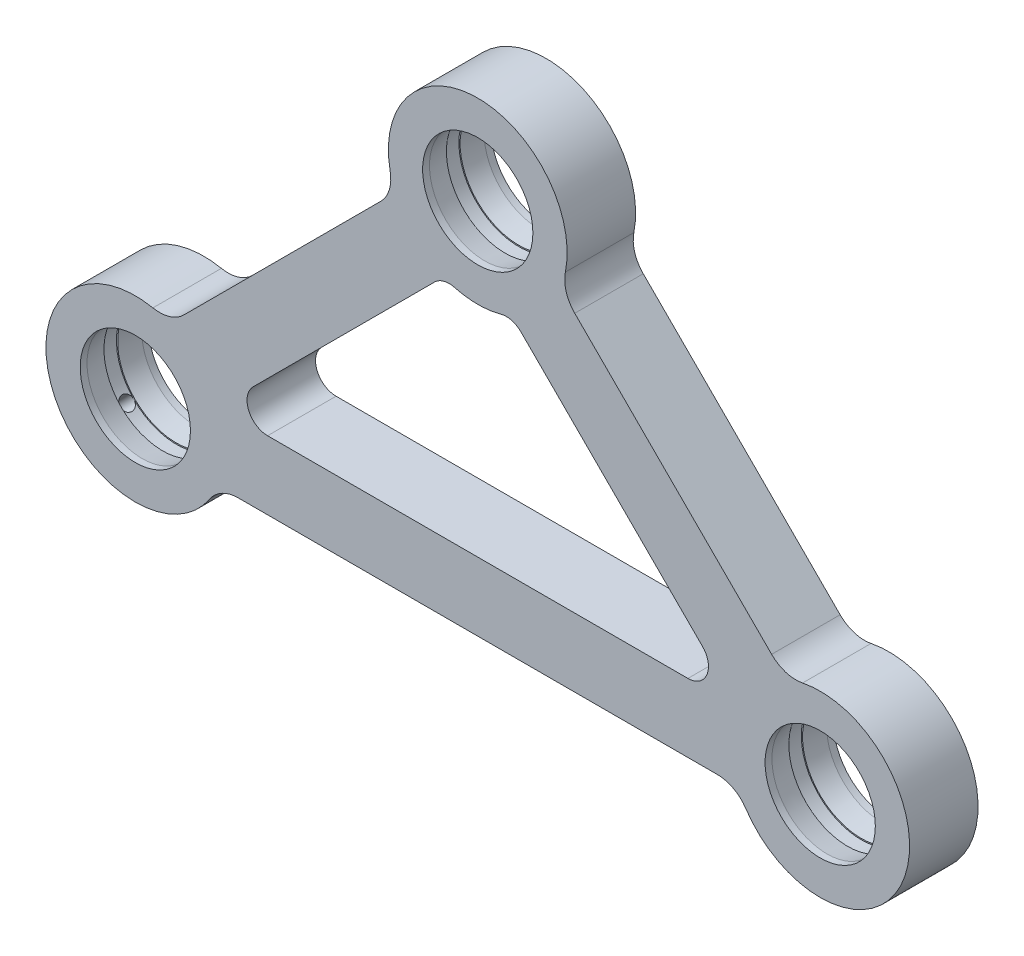
SolidWorks part; units mm, degrees
ref_plane "Front Plane" through (0, 0, 0) normal (0, 0, 1) x (1, 0, 0)
ref_plane "Top Plane" through (0, 0, 0) normal (0, 1, 0) x (1, 0, 0)
ref_plane "Right Plane" through (0, 0, 0) normal (1, 0, 0) x (0, 0, -1)
sketch "Sketch1" plane through (0, 0, 0) normal (0, 0, 1) x (1, 0, 0)
  line L0 (-26.538, 0) -> (73.462, 0) construction
  line L2 (-26.538, 0) -> (23.462, 50) construction
  line L3 (23.462, 50) -> (73.462, 0) construction
  line L4 (-14.4839, 5) -> (61.4078, 5)
  line L5 (-14.4839, -5) -> (61.4078, -5)
  line L6 (-21.55, 12.0591) -> (11.4029, 45.012)
  line L7 (18.474, 37.9409) -> (-14.4789, 4.988)
  line L8 (28.45, 37.9409) -> (61.4029, 4.988)
  line L9 (35.5211, 45.012) -> (68.474, 12.0591)
  circle A0 centre (23.462, 50) radius 8.05
  circle A1 centre (73.462, 0) radius 8.05
  circle A2 centre (-26.538, 0) radius 8.05
  circle A3 centre (-26.538, 0) radius 13.05
  circle A4 centre (23.462, 50) radius 13.05
  circle A5 centre (73.462, 0) radius 13.05
  dimension "D1" = 16.1
  dimension "D2" = 16.1
  dimension "D3" = 16.1
  dimension "D4" = 45
  dimension "D5" = 45
  dimension "D6" = 100
  dimension "D7" = 5
  dimension "D8" = 5
  dimension "D9" = 5
  dimension "D10" = 5
  dimension "D11" = 5
  dimension "D12" = 5
  dimension "D13" = 5
  dimension "D14" = 5
  dimension "D15" = 5
extrude "Boss-Extrude1" add sketch "Sketch1" along normal blind 8 contours A3 A2 | A4 L6 A3 L4 L7 | A4 A0 | A5 L9 A4 L8 L4 | A5 L8 L4 L7 A3 L5 | A5 A1 | A3 L7 L4 | A5 L4 L8 region at (-1.538, 25, 0) region at (-14.4766, 4.996, 0) region at (-14.8224, 4.8528, 0) region at (23.462, 0, 0) region at (48.462, 25, 0) region at (61.4006, 4.996, 0) region at (14.4953, 41.0333, 0) region at (64.4997, 8.9712, 0)
sketch3d "3DSketch1" plane through (0, 0, 0) normal (0, 0, 1) x (1, 0, 0)
  dimension "D1" = 4
sketch "Sketch3" plane through (0, 0, 4) normal (0, 0, 1) x (1, 0, 0)
  circle A0 centre (-26.538, 0) radius 8.7553
  circle A1 centre (23.462, 50) radius 8.7553
  circle A2 centre (73.462, 0) radius 8.7553
  circle A3 centre (-26.538, 0) radius 8.05 construction
  circle A4 centre (23.462, 50) radius 8.05 construction
  circle A5 centre (73.462, 0) radius 8.05 construction
  dimension "D1" = 0.7053
  dimension "D2" = 0.7053
  dimension "D3" = 0.7053
extrude "Cut-Extrude1" cut sketch "Sketch3" against normal blind 1 and the other way blind 1 contours A1 | A0 | A2
sketch3d "3DSketch2" plane through (0, 0, 0) normal (0, 0, 1) x (1, 0, 0)
sketch3d "3DSketch3" plane through (0, 0, 0) normal (0, 0, 1) x (1, 0, 0)
  dimension "D1" = 26
sketch "Sketch4" plane through (0, 62.95, 0) normal (0, -1, 0) x (-1, 0, 0)
  line L0 (-41.8, -4) -> (41.8, -4) construction
  line L1 (-86.512, 0) -> (-86.512, -8) construction
  line L4 (-36.5118, -8) -> (-68.474, -8)
  line L5 (-36.5118, -8) -> (-68.474, -8)
  line L6 (-68.474, -8) -> (-86.512, -8)
  line L7 (-68.474, -8) -> (-86.512, -8)
  line L8 (-86.512, -8) -> (-86.512, 0)
  line L9 (-86.512, -8) -> (-86.512, 0)
  line L10 (-86.512, 0) -> (-68.474, 0)
  line L11 (-86.512, 0) -> (-68.474, 0)
  line L12 (-68.474, 0) -> (-36.5118, 0)
  line L13 (-68.474, 0) -> (-36.5118, 0)
  line L14 (-36.5118, 0) -> (-10.4122, 0)
  line L15 (-36.5118, 0) -> (-10.4122, 0)
  line L16 (-10.4122, 0) -> (21.55, 0)
  line L17 (-10.4122, 0) -> (21.55, 0)
  line L18 (21.55, 0) -> (39.588, 0)
  line L19 (21.55, 0) -> (39.588, 0)
  line L20 (39.588, 0) -> (39.588, -8)
  line L21 (39.588, 0) -> (39.588, -8)
  line L22 (39.588, -8) -> (21.55, -8)
  line L23 (39.588, -8) -> (21.55, -8)
  line L24 (21.55, -8) -> (-10.4122, -8)
  line L25 (21.55, -8) -> (-10.4122, -8)
  line L26 (-10.4122, -8) -> (-36.5118, -8)
  line L27 (-10.4122, -8) -> (-36.5118, -8)
  circle A0 centre (-23.512, -4) radius 1
  dimension "D1" = 2
  dimension "D2" = 63
  dimension "D3" = 126.1
extrude "Cut-Extrude2" cut sketch "Sketch4" along normal blind 6 contours A0
fillet "Fillet1" radius 3 4 edges at (-14.4669, 5, 4) (18.474, 37.9409, 4) (28.45, 37.9409, 4) (61.3909, 5, 4)
fillet "Fillet2" radius 5 6 edges at (68.474, 12.0591, 4) (35.5211, 45.012, 4) (11.4029, 45.012, 4) (-21.55, 12.0591, 4) (-14.4839, -5, 4) (61.4078, -5, 4)
sketch3d "3DSketch4" plane through (0, 0, 0) normal (0, 0, 1) x (1, 0, 0)
sketch3d "3DSketch5" plane through (0, 0, 0) normal (0, 0, 1) x (1, 0, 0)
  dimension "D1" = 26
sketch "Sketch5" plane through (45.888, -45.888, 0) normal (-0.7071, 0.7071, 0) x (0, 0, 1)
  line L0 (8, -31.8152) -> (8, -7.901) construction
  line L1 (8, 43.8955) -> (8, 59.9955) construction
  line L2 (8, 43.8955) -> (8, 59.9955)
  line L7 (8, 64.9955) -> (0, 64.9955) construction
  line L8 (8, 64.9955) -> (0, 64.9955)
  circle A0 centre (4, 51.8955) radius 1
  dimension "D1" = 2
  dimension "D2" = 4
  dimension "D3" = 8
  dimension "D4" = 16.1
  dimension "D5" = 8
extrude "Cut-Extrude3" cut sketch "Sketch5" along normal blind 10 contours A0 region at (82.5837, -9.1924, 4)
draft "Draft4" type of draft neutral plane draft angle 10 faces to draft 3 face at (-18.488, 0, 5) face at (31.512, 50, 5) face at (81.512, 0, 5) neutral plane through (0, 0, 8) neutral plane normal (0, 0, 1) reverse direction yes parameters "D1"=10
draft "Draft6" type of draft neutral plane draft angle 10 faces to draft 3 face at (-18.488, 0, 0) face at (81.512, 0, 0) face at (31.512, 50, 0) neutral plane through (0, 0, 0) neutral plane normal (0, 0, -1) reverse direction yes parameters "D1"=10
sketch3d "3DSketch6" plane through (0, 0, 0) normal (0, 0, 1) x (1, 0, 0)
sketch3d "3DSketch8" plane through (0, 0, 0) normal (0, 0, 1) x (1, 0, 0)
  dimension "D1" = 26
sketch "Sketch6" plane through (-22.426, -22.426, 0) normal (0.7071, 0.7071, 0) x (0, 0, -1)
  line L0 (-8, 31.8152) -> (-8, 5.7152) construction
  line L1 (0, 31.8152) -> (-8, 31.8152) construction
  line L2 (0, 31.8152) -> (-8, 31.8152)
  line L3 (0, 10.7152) -> (0, 26.8152) construction
  line L4 (0, 10.7152) -> (0, 26.8152)
  circle A0 centre (-4, 18.8152) radius 1
  dimension "D1" = 2
  dimension "D2" = 4
  dimension "D3" = 8
  dimension "D4" = 16.1
  dimension "D5" = 8
extrude "Cut-Extrude4" cut sketch "Sketch6" along normal blind 10 contours A0
sketch "Sketch7" plane through (0, 0, 8) normal (0, 0, 1) x (1, 0, 0)
  line L2 (-7.2243, 5) -> (54.1483, 5) construction
  line L5 (17.1588, 36.6257) -> (-9.3456, 10.1213) construction
  line L10 (29.7652, 36.6257) -> (56.2696, 10.1213) construction
  line L11 (66.372, 14.161) -> (37.623, 42.91)
  line L12 (9.301, 42.91) -> (-19.448, 14.161)
  line L13 (-11.5113, -5) -> (58.4353, -5)
  line L14 (66.372, 14.161) -> (37.623, 42.91)
  line L15 (9.301, 42.91) -> (-19.448, 14.161)
  line L16 (-11.5113, -5) -> (58.4353, -5)
  line L17 (-7.2243, 5) -> (54.1483, 5)
  line L18 (17.1588, 36.6257) -> (-9.3456, 10.1213)
  line L19 (29.7652, 36.6257) -> (56.2696, 10.1213)
  circle A36 centre (-26.538, 0) radius 8.05 construction
  arc A37 (-9.3456, 10.1213) -> (-7.2243, 5) centre (-7.2243, 8) ccw construction
  arc A38 (54.1483, 5) -> (56.2696, 10.1213) centre (54.1483, 8) ccw construction
  circle A39 centre (73.462, 0) radius 8.05 construction
  circle A40 centre (23.462, 50) radius 8.05 construction
  arc A41 (29.7652, 36.6257) -> (26.8622, 37.4008) centre (27.6439, 34.5044) ccw construction
  arc A42 (20.0618, 37.4008) -> (26.8622, 37.4008) centre (23.462, 50) ccw construction
  arc A43 (20.0618, 37.4008) -> (17.1588, 36.6257) centre (19.2801, 34.5044) ccw construction
  circle A44 centre (-26.538, 0) radius 8.05
  arc A45 (36.2565, 47.4302) -> (37.623, 42.91) centre (41.1586, 46.4456) ccw
  arc A46 (36.2565, 47.4302) -> (10.6675, 47.4302) centre (23.462, 50) ccw
  arc A47 (9.301, 42.91) -> (10.6675, 47.4302) centre (5.7654, 46.4456) ccw
  arc A48 (-23.9682, 12.7945) -> (-19.448, 14.161) centre (-22.9836, 17.6966) ccw
  arc A49 (-23.9682, 12.7945) -> (-15.6738, -7.2299) centre (-26.538, 0) ccw
  arc A50 (-11.5113, -5) -> (-15.6738, -7.2299) centre (-11.5113, -10) ccw
  arc A51 (62.5978, -7.2299) -> (58.4353, -5) centre (58.4353, -10) ccw
  arc A52 (62.5978, -7.2299) -> (70.8922, 12.7945) centre (73.462, 0) ccw
  arc A53 (66.372, 14.161) -> (70.8922, 12.7945) centre (69.9076, 17.6966) ccw
  arc A54 (36.2565, 47.4302) -> (37.623, 42.91) centre (41.1586, 46.4456) ccw
  arc A55 (36.2565, 47.4302) -> (10.6675, 47.4302) centre (23.462, 50) ccw
  arc A56 (9.301, 42.91) -> (10.6675, 47.4302) centre (5.7654, 46.4456) ccw
  arc A57 (-23.9682, 12.7945) -> (-19.448, 14.161) centre (-22.9836, 17.6966) ccw
  arc A58 (-23.9682, 12.7945) -> (-15.6738, -7.2299) centre (-26.538, 0) ccw
  arc A59 (-11.5113, -5) -> (-15.6738, -7.2299) centre (-11.5113, -10) ccw
  arc A60 (62.5978, -7.2299) -> (58.4353, -5) centre (58.4353, -10) ccw
  arc A61 (62.5978, -7.2299) -> (70.8922, 12.7945) centre (73.462, 0) ccw
  arc A62 (66.372, 14.161) -> (70.8922, 12.7945) centre (69.9076, 17.6966) ccw
  arc A63 (-9.3456, 10.1213) -> (-7.2243, 5) centre (-7.2243, 8) ccw
  arc A64 (54.1483, 5) -> (56.2696, 10.1213) centre (54.1483, 8) ccw
  circle A65 centre (73.462, 0) radius 8.05
  circle A66 centre (23.462, 50) radius 8.05
  arc A67 (29.7652, 36.6257) -> (26.8622, 37.4008) centre (27.6439, 34.5044) ccw
  arc A68 (20.0618, 37.4008) -> (26.8622, 37.4008) centre (23.462, 50) ccw
  arc A69 (20.0618, 37.4008) -> (17.1588, 36.6257) centre (19.2801, 34.5044) ccw
  dimension "D1" = 0
extrude "Boss-Extrude3" add sketch "Sketch7" along normal blind 1
sketch "Sketch11" plane through (0, 0, 0) normal (0, 0, -1) x (-1, 0, 0)
  line L0 (-29.7652, 36.6257) -> (-56.2696, 10.1213) construction
  line L1 (7.2243, 5) -> (-54.1483, 5) construction
  line L2 (-17.1588, 36.6257) -> (9.3456, 10.1213) construction
  line L3 (-37.623, 42.91) -> (-66.372, 14.161)
  line L4 (-58.4353, -5) -> (11.5113, -5)
  line L5 (19.448, 14.161) -> (-9.301, 42.91)
  line L6 (-37.623, 42.91) -> (-66.372, 14.161)
  line L7 (-58.4353, -5) -> (11.5113, -5)
  line L8 (19.448, 14.161) -> (-9.301, 42.91)
  line L9 (-17.1588, 36.6257) -> (9.3456, 10.1213)
  line L10 (7.2243, 5) -> (-54.1483, 5)
  line L11 (-29.7652, 36.6257) -> (-56.2696, 10.1213)
  circle A0 centre (-23.462, 50) radius 8.05 construction
  circle A1 centre (-73.462, 0) radius 8.05
  circle A2 centre (-73.462, 0) radius 8.05
  circle A3 centre (-23.462, 50) radius 8.05
  circle A4 centre (26.538, 0) radius 8.05 construction
  circle A5 centre (26.538, 0) radius 8.05
  arc A6 (-17.1588, 36.6257) -> (-20.0618, 37.4008) centre (-19.2801, 34.5044) ccw construction
  arc A7 (-26.8622, 37.4008) -> (-20.0618, 37.4008) centre (-23.462, 50) ccw construction
  arc A8 (-26.8622, 37.4008) -> (-29.7652, 36.6257) centre (-27.6439, 34.5044) ccw construction
  arc A9 (-56.2696, 10.1213) -> (-54.1483, 5) centre (-54.1483, 8) ccw construction
  arc A10 (7.2243, 5) -> (9.3456, 10.1213) centre (7.2243, 8) ccw construction
  arc A11 (-10.6675, 47.4302) -> (-36.2565, 47.4302) centre (-23.462, 50) ccw
  arc A12 (-37.623, 42.91) -> (-36.2565, 47.4302) centre (-41.1586, 46.4456) ccw
  arc A13 (-70.8922, 12.7945) -> (-66.372, 14.161) centre (-69.9076, 17.6966) ccw
  arc A14 (-70.8922, 12.7945) -> (-62.5978, -7.2299) centre (-73.462, 0) ccw
  arc A15 (-58.4353, -5) -> (-62.5978, -7.2299) centre (-58.4353, -10) ccw
  arc A16 (15.6738, -7.2299) -> (11.5113, -5) centre (11.5113, -10) ccw
  arc A17 (15.6738, -7.2299) -> (23.9682, 12.7945) centre (26.538, 0) ccw
  arc A18 (19.448, 14.161) -> (23.9682, 12.7945) centre (22.9836, 17.6966) ccw
  arc A19 (-10.6675, 47.4302) -> (-9.301, 42.91) centre (-5.7654, 46.4456) ccw
  arc A20 (-10.6675, 47.4302) -> (-36.2565, 47.4302) centre (-23.462, 50) ccw
  arc A21 (-37.623, 42.91) -> (-36.2565, 47.4302) centre (-41.1586, 46.4456) ccw
  arc A22 (-70.8922, 12.7945) -> (-66.372, 14.161) centre (-69.9076, 17.6966) ccw
  arc A23 (-70.8922, 12.7945) -> (-62.5978, -7.2299) centre (-73.462, 0) ccw
  arc A24 (-58.4353, -5) -> (-62.5978, -7.2299) centre (-58.4353, -10) ccw
  arc A25 (15.6738, -7.2299) -> (11.5113, -5) centre (11.5113, -10) ccw
  arc A26 (15.6738, -7.2299) -> (23.9682, 12.7945) centre (26.538, 0) ccw
  arc A27 (19.448, 14.161) -> (23.9682, 12.7945) centre (22.9836, 17.6966) ccw
  arc A28 (-10.6675, 47.4302) -> (-9.301, 42.91) centre (-5.7654, 46.4456) ccw
  arc A29 (7.2243, 5) -> (9.3456, 10.1213) centre (7.2243, 8) ccw
  arc A30 (-56.2696, 10.1213) -> (-54.1483, 5) centre (-54.1483, 8) ccw
  arc A31 (-26.8622, 37.4008) -> (-29.7652, 36.6257) centre (-27.6439, 34.5044) ccw
  arc A32 (-26.8622, 37.4008) -> (-20.0618, 37.4008) centre (-23.462, 50) ccw
  arc A33 (-17.1588, 36.6257) -> (-20.0618, 37.4008) centre (-19.2801, 34.5044) ccw
  dimension "D1" = 0
  dimension "D2" = 0
extrude "Boss-Extrude4" add sketch "Sketch11" along normal blind 1
equation "\"D2@Sketch1\"=\"D1@Sketch1\""
equation "\"D3@Sketch1\"=\"D1@Sketch1\""
equation "\"D5@Sketch1\"=\"D4@Sketch1\""
equation "\"D8@Sketch1\"=\"D7@Sketch1\""
equation "\"D9@Sketch1\"=\"D7@Sketch1\""
equation "\"D11@Sketch1\"=\"D10@Sketch1\""
equation "\"D12@Sketch1\"=\"D10@Sketch1\""
equation "\"D13@Sketch1\"=\"D10@Sketch1\""
equation "\"D14@Sketch1\"=\"D13@Sketch1\""
equation "\"D15@Sketch1\"=\"D14@Sketch1\""
equation "\"D2@Sketch3\"=\"D1@Sketch3\""
equation "\"D3@Sketch3\"=\"D1@Sketch3\""
equation "\"D2@Sketch4\"=\"D3@Sketch4\"/2"
equation "\"D3@Sketch5\"=\"D4@Sketch5\"/2"
equation "\"D2@Sketch5\"=\"D5@Sketch5\"/2"
equation "\"D2@Sketch6\"=\"D3@Sketch6\"/2"
equation "\"D5@Sketch6\"=\"D4@Sketch6\"/2"
equation "\"D1@Sketch3\"=4*tan(10)"
